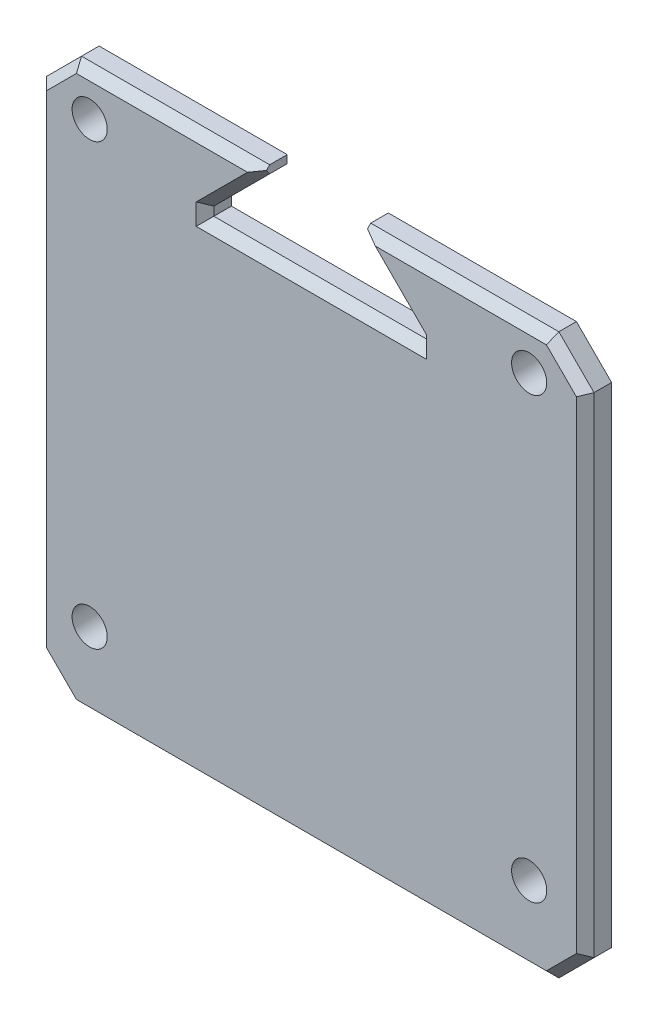
SolidWorks part; units mm, degrees
ref_plane "Front Plane" through (0, 0, 0) normal (0, 0, 1) x (1, 0, 0)
ref_plane "Top Plane" through (0, 0, 0) normal (0, 1, 0) x (1, 0, 0)
ref_plane "Right Plane" through (0, 0, 0) normal (1, 0, 0) x (0, 0, -1)
sketch "Sketch1" plane through (0, 0, 0) normal (0, 0, 1) x (1, 0, 0)
  line L0 (-23.9214, -14.934) -> (-23.9214, -2.684)
  line L1 (-23.9214, -2.684) -> (-24.9214, -1.684)
  line L2 (-24.9214, -1.684) -> (-26.4214, -1.684)
  line L3 (-26.4214, -1.684) -> (-26.4214, 8.316)
  line L4 (-26.4214, 8.316) -> (-24.9214, 8.316)
  line L5 (-24.9214, 8.316) -> (-23.9214, 9.316)
  line L6 (-23.9214, 9.316) -> (-23.9214, 21.566)
  line L7 (-23.9214, 21.566) -> (-18.4214, 27.066)
  line L8 (-18.4214, 27.066) -> (-9.2714, 27.066)
  line L9 (-9.2714, 27.066) -> (-5.2714, 31.066)
  line L10 (-5.2714, 31.066) -> (-5.2714, 32.066)
  line L11 (-5.2714, 32.066) -> (-26.9214, 32.066)
  line L12 (-26.9214, 32.066) -> (-30.9214, 28.066)
  line L13 (-30.9214, 28.066) -> (-30.9214, -27.6088)
  line L14 (-30.9214, -27.6088) -> (-26.9214, -31.6088)
  line L15 (-26.9214, -31.6088) -> (27.3786, -31.6088)
  line L16 (27.3786, -31.6088) -> (31.3786, -27.6088)
  line L17 (31.3786, -27.6088) -> (31.3786, 28.066)
  line L18 (31.3786, 28.066) -> (27.3786, 32.066)
  line L19 (27.3786, 32.066) -> (5.7286, 32.066)
  line L20 (5.7286, 32.066) -> (5.7286, 31.066)
  line L21 (5.7286, 31.066) -> (9.7286, 27.066)
  line L22 (9.7286, 27.066) -> (18.8786, 27.066)
  line L23 (18.8786, 27.066) -> (24.3786, 21.566)
  line L24 (24.3786, 21.566) -> (24.3786, -14.934)
  line L25 (24.3786, -14.934) -> (18.8786, -20.434)
  line L26 (18.8786, -20.434) -> (18.5874, -20.434)
  line L27 (18.5874, -20.434) -> (21.5751, -25.6088)
  line L28 (21.5751, -25.6088) -> (-21.1178, -25.6088)
  line L29 (-21.1178, -25.6088) -> (-18.1301, -20.434)
  line L30 (-18.1301, -20.434) -> (-18.4214, -20.434)
  line L31 (-18.4214, -20.434) -> (-23.9214, -14.934)
sketch "Sketch3" plane through (0, 0, 0) normal (0, 0, 1) x (1, 0, 0)
  line L0 (-26.9214, -31.6088) -> (27.3786, -31.6088) construction
  line L1 (-26.9214, 32.066) -> (27.3786, 32.066)
  line L2 (-30.9214, 28.066) -> (-30.9214, -27.6088)
  line L3 (-26.9214, -31.6088) -> (27.3786, -31.6088)
  line L4 (31.3786, 28.066) -> (31.3786, -27.6088)
  line L7 (-30.9214, 28.066) -> (-26.9214, 32.066)
  line L8 (27.3786, 32.066) -> (31.3786, 28.066)
  line L9 (27.3786, -31.6088) -> (31.3786, -27.6088)
  line L10 (-30.9214, -27.6088) -> (-26.9214, -31.6088)
  line L11 (-5.2714, 32.066) -> (-26.9214, 32.066) construction
  line L12 (31.3786, -27.6088) -> (31.3786, 28.066) construction
  line L13 (-30.9214, 28.066) -> (-30.9214, -27.6088) construction
  point P0 (-30.9214, 32.066)
  point P1 (31.3786, -31.6088)
  point P2 (-30.9214, -31.6088)
  point P3 (31.3786, 32.066)
extrude "Boss-Extrude1" add sketch "Sketch3" along normal blind 3
sketch "Sketch2" plane through (0, 0, 0) normal (0, 0, 1) x (1, 0, 0)
  line L0 (-5.2714, 32.066) -> (-5.2714, 31.066) construction
  line L1 (-5.2714, 31.066) -> (-11.2714, 25.066) construction
  line L2 (-11.2714, 25.066) -> (11.7286, 25.066) construction
  line L3 (11.7286, 25.066) -> (5.7286, 31.066) construction
  line L4 (5.7286, 31.066) -> (5.7286, 32.066) construction
  line L5 (5.7286, 32.066) -> (-5.2714, 32.066) construction
  line L6 (-9.2714, 27.066) -> (-5.2714, 31.066) construction
  line L7 (5.7286, 31.066) -> (9.7286, 27.066) construction
  line L14 (-11.8749, 24.816) -> (-11.8749, 23.816)
  line L15 (-11.8749, 23.816) -> (12.3322, 23.816)
  line L16 (12.3322, 24.816) -> (5.9786, 31.1696)
  line L17 (5.9786, 31.1696) -> (5.9786, 32.316)
  line L18 (5.9786, 32.316) -> (-5.5214, 32.316)
  line L19 (-5.5214, 32.316) -> (-5.5214, 31.1696)
  line L20 (-5.5214, 31.1696) -> (-11.8749, 24.816)
  line L21 (-11.8749, 24.816) -> (12.3322, 24.816) construction
  line L22 (12.3322, 23.816) -> (12.3322, 24.816)
  dimension "D1" = 23
  dimension "D2" = 0.25
  dimension "D3" = 1
extrude "Cut-Extrude4" cut sketch "Sketch2" along normal blind 10 contours L20 L21 L16 L17 L18 L19 region at (0.2286, 27.4471, 0)
sketch "Sketch4" plane through (0, 0, 3) normal (0, 0, 1) x (1, 0, 0)
  line L1 (-975.6214, 3.316) -> (49024.3786, 3.316) construction
  line L3 (24.3786, 21.566) -> (24.3786, -14.934) construction
  circle A0 centre (-25, 27.316) radius 2
  circle A1 centre (25, 27.316) radius 2
  circle A2 centre (25, -22.684) radius 2
  circle A3 centre (-25, -22.684) radius 2
  point P18 (24.3786, 3.316)
  dimension "D3" = 4
  dimension "D6" = 4
  dimension "D7" = 4
  dimension "D8" = 4
  dimension "D1" = 24
  dimension "D2" = 25
  dimension "D4" = 26
  dimension "D5" = 25
chamfer "Chamfer1" distance 1 angle 45 14 edges at (16.6786, 32.066, 3) (29.3786, 30.066, 3) (31.3786, 0.2286, 3) (29.3786, -29.6088, 3) (0.2286, -31.6088, 3) (-28.9214, -29.6088, 3) (-30.9214, 0.2286, 3) (-28.9214, 30.066, 3) (-16.2214, 32.066, 3) (-8.6981, 27.9928, 3) (9.1554, 27.9928, 3) (-11.8749, 24.316, 3) (0.2286, 23.816, 3) (12.3322, 24.316, 3)
extrude "Cut-Extrude5" cut sketch "Sketch4" against normal blind 10
